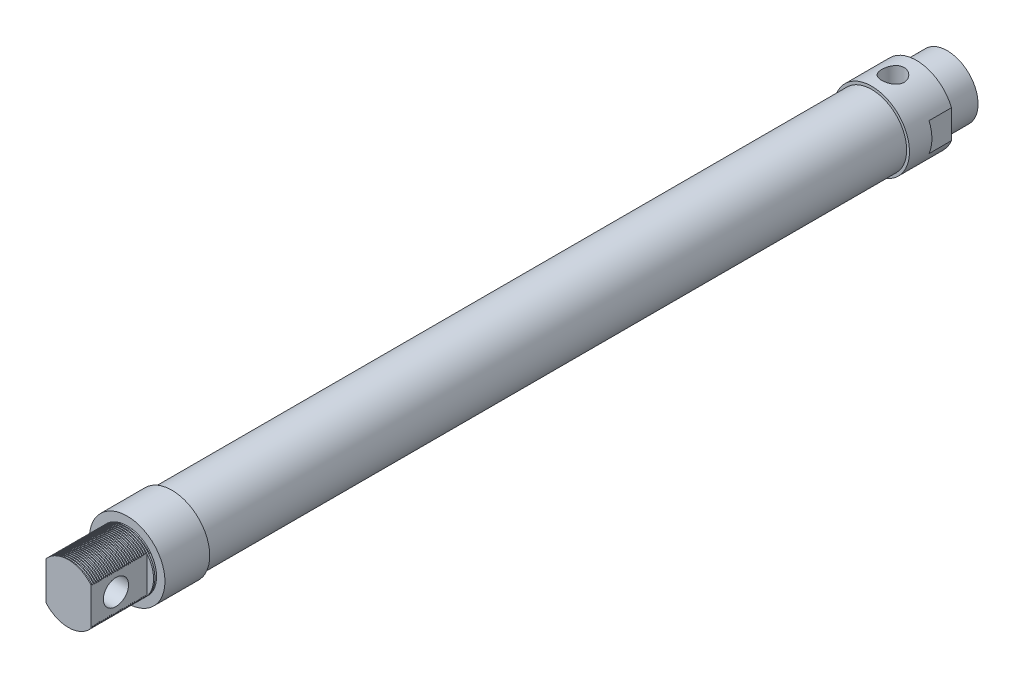
SolidWorks part; units mm, degrees
ref_plane "Front Plane" through (0, 0, 0) normal (0, 0, 1) x (1, 0, 0)
ref_plane "Top Plane" through (0, 0, 0) normal (0, 1, 0) x (1, 0, 0)
ref_plane "Right Plane" through (0, 0, 0) normal (1, 0, 0) x (0, 0, -1)
sketch "Sketch1" plane through (0, 0, 0) normal (0, 0, 1) x (1, 0, 0)
  circle A0 centre (0, 0) radius 12.5
extrude "Boss-Extrude1" add sketch "Sketch1" along normal blind 250
sketch "Sketch2" plane through (0, 0, 250) normal (0, 0, 1) x (1, 0, 0)
  circle A2 centre (0, 0) radius 13.5
extrude "Boss-Extrude2" add sketch "Sketch2" along normal blind 16
sketch "Sketch3" plane through (0, 0, 266) normal (0, 0, 1) x (1, 0, 0)
  circle A0 centre (0, 0) radius 10.5
extrude "Boss-Extrude3" add sketch "Sketch3" along normal blind 1
sketch "Sketch4" plane through (0, 0, 267) normal (0, 0, 1) x (1, 0, 0)
  line L0 (0, 14.408) -> (0, -15.9361) construction
  line L1 (-8, 6.8007) -> (-8, -6.8007)
  line L2 (8, 6.8007) -> (8, -6.8007)
  line L4 (-8, 14.408) -> (-8, -15.9361) construction
  line L5 (8, 14.408) -> (8, -15.9361) construction
  circle A1 centre (0, 0) radius 10.5
  arc A2 (-8, -6.8007) -> (8, -6.8007) centre (0, 0) ccw
  arc A3 (8, 6.8007) -> (-8, 6.8007) centre (0, 0) ccw
  dimension "D2" = 8
  dimension "D1" = 0
  dimension "D3" = 8
extrude "Boss-Extrude4" add sketch "Sketch4" along normal blind 20
sketch "Sketch5" plane through (-8, 0, 0) normal (-1, 0, 0) x (0, 0, 1)
  line L0 (287, 6.8007) -> (287, -6.8007) construction
  circle A0 centre (278, 0) radius 4.5
  dimension "D1" = 9
extrude "Cut-Extrude1" cut sketch "Sketch5" against normal through all
sketch "Sketch7" plane through (0, 0, 287) normal (0, 0, 1) x (1, 0, 0)
  circle A0 centre (0, 0) radius 10.5
curve "Helix/Spiral1" pitch 0.75 height 20.625 turns 27.5
ref_plane "Plane1" through (-8.3857, -6.3191, 287) normal (-0.6018, 0.7986, -0.0114) x (-0.7987, -0.6017, 0.0069)
sketch "Sketch8" plane through (-8.3857, -6.3191, 287) normal (-0.6018, 0.7986, -0.0114) x (-0.7987, -0.6017, 0.0069)
  line L1 (0.0179, -0.4657) -> (0, 0)
  line L2 (0, 0) -> (-0.3925, -0.242)
  line L3 (-0.3925, -0.242) -> (0.0179, -0.4657)
sweep "Cut-Sweep1" cut profiles "Sketch8" path "Helix/Spiral1"
sketch "Sketch9" plane through (0, 0, 0) normal (0, 0, -1) x (-1, 0, 0)
  circle A0 centre (0, 0) radius 13.5 construction
  circle A1 centre (0, 0) radius 13.5
extrude "Boss-Extrude5" add sketch "Sketch9" along normal blind 8
sketch "Sketch10" plane through (0, 0, -8) normal (0, 0, -1) x (-1, 0, 0)
  line L0 (0, 0) -> (0, 13.5) construction
  line L1 (12.5, -5.099) -> (12.5, 5.099)
  line L2 (-12.5, -5.099) -> (-12.5, 5.099)
  line L4 (-12.5, 0) -> (-12.5, 13.5) construction
  line L5 (12.5, 0) -> (12.5, 13.5) construction
  arc A0 (12.5, 5.099) -> (-12.5, 5.099) centre (0, 0) ccw
  circle A1 centre (0, 0) radius 13.5
  arc A2 (-12.5, -5.099) -> (12.5, -5.099) centre (0, 0) ccw
  dimension "D2" = 12.5
  dimension "D1" = 0
  dimension "D3" = 12.5
extrude "Boss-Extrude6" add sketch "Sketch10" along normal blind 8
sketch "Sketch11" plane through (0, 0, -16) normal (0, 0, -1) x (-1, 0, 0)
  circle A0 centre (0, 0) radius 11
extrude "Boss-Extrude7" add sketch "Sketch11" along normal blind 11
sketch "Sketch12" plane through (0, 0, -27) normal (0, 0, -1) x (-1, 0, 0)
  circle A1 centre (0, 0) radius 11
  circle A2 centre (0, 0) radius 11
  dimension "D1" = 0
ref_plane "Plane3" through (0, 13.5, 0) normal (0, 1, 0) x (-1, 0, 0)
sketch "Sketch14" plane through (0, 13.5, 0) normal (0, 1, 0) x (-1, 0, 0)
  circle A0 centre (0, -7.5937) radius 4
extrude "Cut-Extrude2" cut sketch "Sketch14" against normal blind 6
ref_plane "Plane4" through (0, 13.5, 0) normal (0, 1, 0) x (0, 0, -1)
sketch "Sketch16" plane through (0, 0, -27) normal (0, 0, -1) x (-1, 0, 0)
  circle A0 centre (0, 0) radius 4
extrude "Cut-Extrude4" cut sketch "Sketch16" against normal blind 100
